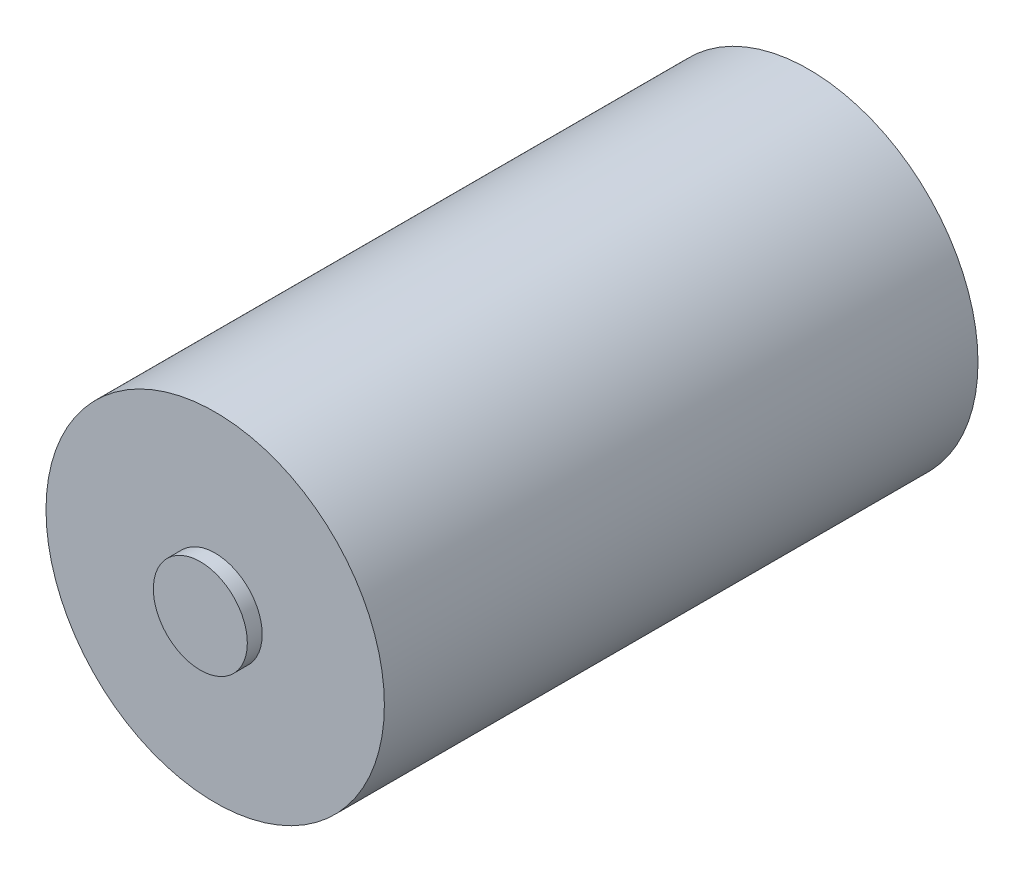
SolidWorks part; units mm, degrees
ref_plane "Plan de face" through (0, 0, 0) normal (0, 0, 1) x (1, 0, 0)
ref_plane "Plan de dessus" through (0, 0, 0) normal (0, 1, 0) x (1, 0, 0)
ref_plane "Plan de droite" through (0, 0, 0) normal (1, 0, 0) x (0, 0, -1)
sketch "Esquisse1" plane through (0, 0, 0) normal (0, 0, 1) x (1, 0, 0)
  circle A0 centre (0, 0) radius 17.1
  dimension "D1" = 34.2
extrude "Boss.-Extru.1" add sketch "Esquisse1" along normal blind 61.5
sketch "Esquisse2" plane through (0, 0, 61.5) normal (0, 0, 1) x (1, 0, 0)
  circle A0 centre (0, 0) radius 4.75
  circle A1 centre (0, 0) radius 17.1
  circle A2 centre (0, 0) radius 17.1 construction
  dimension "D1" = 9.5
extrude "Enlèv. mat.-Extru.1" cut sketch "Esquisse2" against normal blind 1.5
sketch3d "3DSketch3" plane through (0, 0, 0) normal (0, 0, 1) x (1, 0, 0)
sketch "Sketch2" plane through (3.3394, -16.7708, 0) normal (0.1953, -0.9807, 0) x (-0.9807, -0.1953, 0)
  line L0 (1.2994, -54.6514) -> (-30.3966, -54.6514) construction
  line L5 (1.2994, -2.3593) -> (-13.3732, -2.3593) construction
  text T0 "+" font "Century Gothic" height in points 18
  text T1 "-" font "Century Gothic" height in points 18
wrap "Wrap1" sketch "Sketch2" wrap type scribe source sketch "Sketch2"
